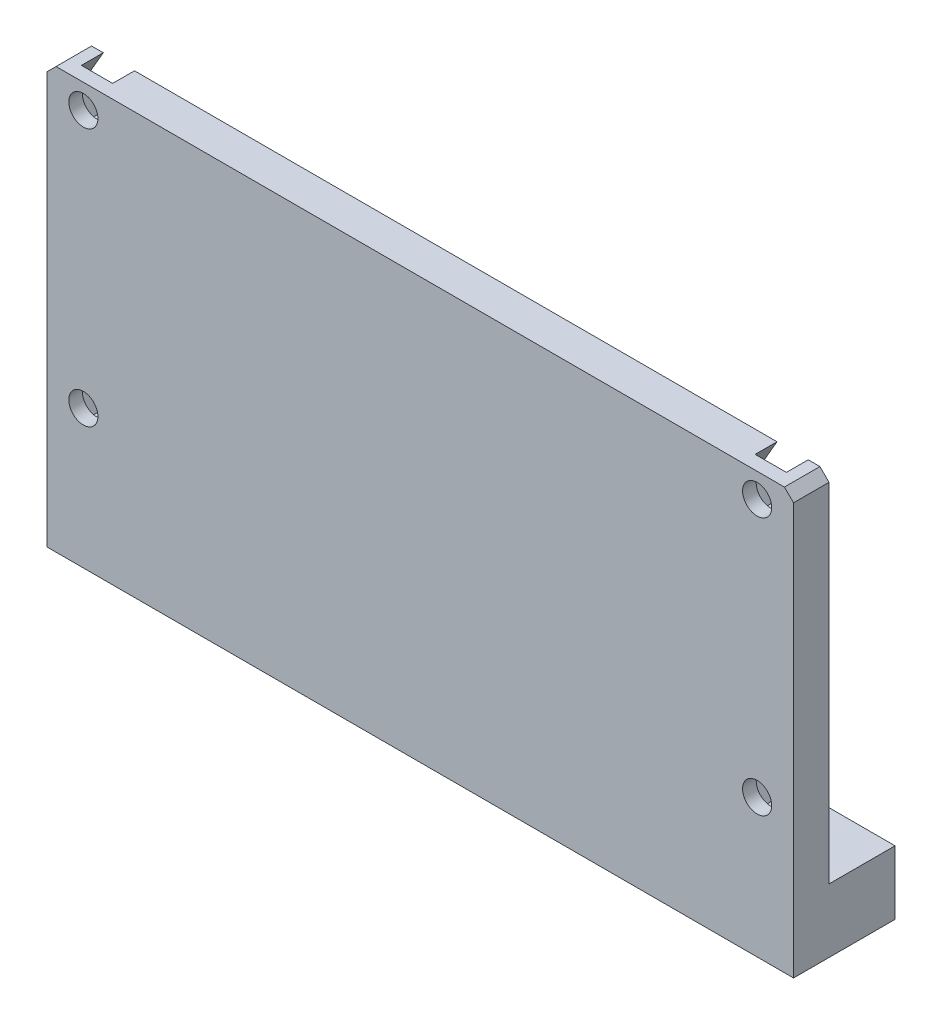
SolidWorks part; units mm, degrees
ref_plane "Front Plane" through (0, 0, 0) normal (0, 0, 1) x (1, 0, 0)
ref_plane "Top Plane" through (0, 0, 0) normal (0, 1, 0) x (1, 0, 0)
ref_plane "Right Plane" through (0, 0, 0) normal (1, 0, 0) x (0, 0, -1)
sketch "Sketch1" plane through (0, 0, 0) normal (0, 0, 1) x (1, 0, 0)
  line L0 (1, 11.6) -> (0, 10.6) construction
  line L1 (81, 11.6) -> (1, 11.6) construction
  line L2 (82, 10.6) -> (81, 11.6) construction
  line L3 (0, -35.2) -> (82, -35.2)
  line L4 (1, 11.6) -> (0, 10.6)
  line L5 (81, 11.6) -> (1, 11.6)
  line L6 (82, 10.6) -> (81, 11.6)
  line L9 (82, -35.2) -> (82, 10.6)
  line L10 (0, 10.6) -> (0, -35.2)
  line L11 (4, 8.9396) -> (4, -41.6656) construction
  circle A0 centre (4, 8.9396) radius 1.6 construction
  circle A1 centre (78, 8.9396) radius 1.6 construction
  circle A2 centre (4, -29.89) radius 1.6 construction
  circle A3 centre (4, 8.9396) radius 1.6
  circle A4 centre (78, 8.9396) radius 1.6
  dimension "D1" = 46.8
extrude "Boss-Extrude1" add sketch "Sketch1" along normal blind 11.15 contours A3 | L5 L4 L10 L3 L9 L6 | A4 region at (4, 8.9396, 0)
sketch "Sketch2" plane through (0, 0, 0) normal (0, 0, -1) x (-1, 0, 0)
  line L0 (0, -49.6) -> (-82, -49.6) construction
  line L1 (0, -49.6) -> (-82, -49.6) construction
  line L2 (-82, -54.6) -> (0, -54.6)
  line L3 (-82, -34.6) -> (0, -34.6)
  line L4 (-82, -35.2) -> (-82, 10.6) construction
  line L5 (0, 10.6) -> (0, -35.2) construction
  line L7 (0, -34.6) -> (0, -35.2)
  line L8 (-82, -35.2) -> (-82, -34.6)
  line L9 (-82, -35.2) -> (0, -35.2)
  dimension "D1" = 5
  dimension "D2" = 20
extrude "Cut-Extrude1" cut sketch "Sketch2" against normal blind 8 contours L3 L7 L9 L8
sketch "Sketch3" plane through (0, -34.6, 0) normal (0, -1, 0) x (1, 0, 0)
  line L0 (10.85, 4) -> (10.85, 0)
  line L1 (14.15, 4) -> (14.15, 0)
  line L2 (16.75, 4) -> (16.75, 0)
  line L3 (23.25, 4) -> (23.25, 0)
  line L4 (0, 0) -> (82, 0)
  line L5 (82, 0) -> (82, 8)
  line L6 (82, 8) -> (0, 8)
  line L7 (0, 8) -> (0, 0)
  line L8 (10.85, 0) -> (14.15, 0)
  line L9 (82, 0) -> (82, 8)
  line L10 (82, 8) -> (0, 8)
  line L11 (0, 8) -> (0, 0)
  line L12 (25.85, 4) -> (25.85, 0)
  line L13 (29.15, 4) -> (29.15, 0)
  line L14 (25.85, 0) -> (82, 0)
  line L15 (16.75, 0) -> (23.25, 0)
  arc A0 (14.15, 4) -> (10.85, 4) centre (12.5, 4) ccw
  arc A1 (23.25, 4) -> (16.75, 4) centre (20, 4) ccw
  arc A2 (29.15, 4) -> (25.85, 4) centre (27.5, 4) ccw
  line M5 (0, 0) -> (82, 0)
  dimension "D2" = 3.3
  dimension "D3" = 3.3
  dimension "D4" = 15
  dimension "D5" = 7.5
  dimension "D6" = 6.5
  dimension "D7" = 20
  dimension "D1" = 0
extrude "Cut-Extrude2" cut sketch "Sketch3" against normal up to next contours L13 A2 L12 M5 | A0 L0 L8 L1 | A1 L2 L15 L3 region at (27.5, -34.6, 2.6608)
sketch "Sketch4" plane through (0, 11.6, 0) normal (0, 1, 0) x (1, 0, 0)
  line L0 (9.25, -4) -> (9.25, 0)
  line L1 (10.85, 0) -> (1, 0) construction
  line L2 (15.75, -4) -> (15.75, 0)
  line L3 (16.75, 0) -> (14.15, 0) construction
  line L4 (15.75, 0) -> (9.25, 0)
  line L5 (24.25, -4) -> (24.25, 0)
  line L6 (25.85, 0) -> (23.25, 0) construction
  line L7 (24.25, 0) -> (30.75, 0)
  line L8 (81, 0) -> (29.15, 0) construction
  line L9 (30.75, 0) -> (30.75, -4)
  arc A0 (10.85, -4) -> (14.15, -4) centre (12.5, -4) ccw construction
  arc A1 (25.85, -4) -> (29.15, -4) centre (27.5, -4) ccw construction
  arc A2 (10.85, -4) -> (14.15, -4) centre (12.5, -4) ccw construction
  arc A3 (25.85, -4) -> (29.15, -4) centre (27.5, -4) ccw construction
  arc A4 (9.25, -4) -> (15.75, -4) centre (12.5, -4) ccw
  arc A5 (24.25, -4) -> (30.75, -4) centre (27.5, -4) ccw
  dimension "D1" = 6.5
  dimension "D2" = 6.5
extrude "Cut-Extrude3" cut sketch "Sketch4" against normal offset from surface (40.2 mm away) 6 up to face at (25.25, -34.6, 2.9094)
sketch "Sketch6" plane through (0, 11.6, 0) normal (0, 1, 0) x (1, 0, 0)
  line L0 (15.75, -4) -> (15.75, 0) construction
  line L1 (24.25, 0) -> (24.25, -4) construction
  line L2 (15.75, -4) -> (15.75, 0)
  line L3 (24.25, 0) -> (24.25, -4)
  line L4 (12.5, -7.25) -> (0, -7.25)
  line L5 (0, -11.15) -> (0, 0) construction
  line L6 (0, -7.25) -> (0, 1.0612)
  line L7 (0, 1.0612) -> (15.75, 1.0612)
  line L8 (15.75, 1.0612) -> (15.75, 0)
  line L9 (27.5, -7.25) -> (41, -7.25)
  line L10 (41, -7.25) -> (41, 0)
  line L11 (81, 0) -> (30.75, 0) construction
  line L12 (41, 0) -> (24.25, 0)
  arc A0 (9.25, -4) -> (15.75, -4) centre (12.5, -4) ccw construction
  arc A1 (24.25, -4) -> (30.75, -4) centre (27.5, -4) ccw construction
  arc A2 (12.5, -7.25) -> (15.75, -4) centre (12.5, -4) ccw
  arc A3 (24.25, -4) -> (27.5, -7.25) centre (27.5, -4) ccw
  dimension "D1" = 41
extrude "Cut-Extrude5" cut sketch "Sketch6" against normal offset from surface (39.2 mm away) 7 up to face at (25.25, -34.6, 2.9094)
ref_plane "Plane1" through (41, 0, 0) normal (-1, 0, 0) x (0, 0, 1)
mirror "Mirror1" about plane through (41, 0, 0) normal (-1, 0, 0) of "Cut-Extrude5", "Cut-Extrude3", "Cut-Extrude2", "Cut-Extrude1"
sketch "Sketch8" plane through (0, 0, 8) normal (0, 0, -1) x (-1, 0, 0)
  line L4 (-82, -34.6) -> (-82, -35.2)
  line L5 (-82, -35.2) -> (0, -35.2)
  line L6 (0, -35.2) -> (0, -34.6)
  line L7 (0, -34.6) -> (-82, -34.6)
  line L8 (-82, -34.6) -> (-82, -35.2)
  line L9 (-82, -35.2) -> (0, -35.2)
  line L10 (0, -35.2) -> (0, -34.6)
  line L11 (0, -34.6) -> (-82, -34.6)
  dimension "D1" = 0
sketch "Sketch9" plane through (0, 0, 0) normal (-1, 0, 0) x (0, 0, 1)
  line L2 (7.25, 11.6) -> (0, 2.4)
  line L3 (0, 11.6) -> (7.25, 11.6)
sketch "Sketch12" plane through (0, 11.6, 0) normal (0, 1, 0) x (1, 0, 0)
  line L0 (16.75, -4) -> (16.75, 0)
  line L1 (16.75, 0) -> (18, 0)
  line L2 (23.25, 0) -> (23.25, -4)
  line L5 (22, 0) -> (23.25, 0)
  line L6 (58.75, -4) -> (58.75, 0)
  line L7 (58.75, 0) -> (60.05, 0)
  line L8 (65.25, 0) -> (65.25, -4) construction
  line L9 (65.25, 0) -> (65.25, -4)
  line L10 (60.05, 0) -> (60.155, -3.1064)
  line L11 (18, 0) -> (18.11, -3.0846)
  line L12 (63.95, 0) -> (65.25, 0)
  line L13 (22, 0) -> (21.89, -3.0846)
  line L15 (63.95, 0) -> (63.845, -3.1064)
  arc A0 (16.75, -4) -> (23.25, -4) centre (20, -4) ccw construction
  arc A1 (58.75, -4) -> (65.25, -4) centre (62, -4) ccw construction
  arc A2 (16.75, -4) -> (23.25, -4) centre (20, -4) ccw
  arc A3 (58.75, -4) -> (65.25, -4) centre (62, -4) ccw
  arc A4 (18.11, -3.0846) -> (21.89, -3.0846) centre (20, -4) ccw
  arc A5 (60.155, -3.1064) -> (63.845, -3.1064) centre (62, -4) ccw
  dimension "D1" = 1.25
  dimension "D2" = 4.1
  dimension "D3" = 1.3
  dimension "D4" = 1.3
  dimension "D5" = 1.25
extrude "Boss-Extrude2" add sketch "Sketch12" against normal offset from surface (32.2 mm away) 7 up to face at (41, -27.6, 3.9744)
chamfer "Chamfer3" distance 1.1 angle 45 3 edges at (58.75, -20.6, 2) (65.25, -20.6, 2) (62, -20.6, 7.25)
chamfer "Chamfer4" distance 1.1 angle 45 3 edges at (16.75, -20.6, 2) (23.25, -20.6, 2) (20, -20.6, 7.25)
extrude "Cut-Extrude12" cut sketch "Sketch9" against normal through all and the other way through all flip side to cut contours L3 L2
fillet "Fillet3" radius 15 4 edges at (16.875, 2.4, 0) (23.125, 2.4, 0) (58.9, 2.4, 0) (65.1, 2.4, 0)
sketch "Sketch13" plane through (0, 0, 7.25) normal (0, 0, -1) x (-1, 0, 0)
  circle A0 centre (-78, 8.9396) radius 2.85
  dimension "D1" = 5.7
sketch "Sketch14" plane through (0, 0, 11.15) normal (0, 0, 1) x (1, 0, 0)
  circle A0 centre (4, -19.4004) radius 1.6 construction
  circle A1 centre (4, -19.4004) radius 1.6
extrude "Cut-Extrude14" cut sketch "Sketch14" against normal through all contours A1
mirror "Mirror3" about plane through (41, 0, 0) normal (-1, 0, 0) of "Cut-Extrude14"
sketch "Sketch18" plane through (0, -27.6, 0) normal (0, 1, 0) x (1, 0, 0)
  line L6 (14.15, 0) -> (14.15, -4)
  line L7 (10.85, -4) -> (10.85, 0)
  line L8 (10.85, 0) -> (9.25, 0)
  line L9 (9.25, 0) -> (9.25, -4)
  line L10 (15.75, -4) -> (15.75, 0)
  line L11 (15.75, 0) -> (14.15, 0)
  line L12 (14.15, 0) -> (14.15, -1.2)
  line L13 (10.85, -1.2) -> (10.85, 0)
  line L14 (10.85, 0) -> (9.25, 0)
  line L15 (9.25, 0) -> (9.25, -4)
  line L16 (15.75, -4) -> (15.75, 0)
  line L17 (15.75, 0) -> (14.15, 0)
  line L18 (29.15, 0) -> (29.15, -4)
  line L19 (25.85, -4) -> (25.85, 0)
  line L20 (25.85, 0) -> (24.25, 0)
  line L21 (24.25, 0) -> (24.25, -4)
  line L22 (30.75, -4) -> (30.75, 0)
  line L23 (30.75, 0) -> (29.15, 0)
  line L24 (29.15, 0) -> (29.15, -1.2)
  line L25 (25.85, -1.2) -> (25.85, 0)
  line L26 (25.85, 0) -> (24.25, 0)
  line L27 (24.25, 0) -> (24.25, -4)
  line L28 (30.75, -4) -> (30.75, 0)
  line L29 (30.75, 0) -> (29.15, 0)
  arc A0 (10.85, -1.2) -> (9.25, -4) centre (12.5, -4) ccw
  arc A1 (15.75, -4) -> (14.15, -1.2) centre (12.5, -4) ccw
  arc A2 (10.85, -4) -> (14.15, -4) centre (12.5, -4) ccw
  arc A3 (9.25, -4) -> (15.75, -4) centre (12.5, -4) ccw
  arc A4 (25.85, -1.2) -> (24.25, -4) centre (27.5, -4) ccw
  arc A5 (30.75, -4) -> (29.15, -1.2) centre (27.5, -4) ccw
  arc A6 (25.85, -4) -> (29.15, -4) centre (27.5, -4) ccw
  arc A7 (24.25, -4) -> (30.75, -4) centre (27.5, -4) ccw
  dimension "D1" = 0
  dimension "D2" = 0
extrude "Boss-Extrude3" add sketch "Sketch18" against normal blind 3.5
mirror "Mirror5" about plane through (41, 0, 0) normal (-1, 0, 0) of "Boss-Extrude3"
sketch "Sketch19" plane through (0, 0, 7.25) normal (0, 0, -1) x (-1, 0, 0)
  circle A0 centre (-78, -19.4004) radius 2.85
extrude "Cut-Extrude16" cut sketch "Sketch8" against normal through all contours L11 L8 L9 L10
sketch "Sketch20" plane through (0, 0, 7.25) normal (0, 0, -1) x (-1, 0, 0)
  line L1 (-76.375, 11.7542) -> (-79.625, 11.7542)
  line L2 (-79.625, 11.7542) -> (-81.25, 8.9396)
  line L3 (-81.25, 8.9396) -> (-79.625, 6.1251)
  line L4 (-79.625, 6.1251) -> (-76.375, 6.1251)
  line L5 (-76.375, 6.1251) -> (-74.75, 8.9396)
  line L6 (-74.75, 8.9396) -> (-76.375, 11.7542)
  line L7 (-79.625, -16.5858) -> (-81.25, -19.4004)
  line L8 (-81.25, -19.4004) -> (-79.625, -22.2149)
  line L9 (-79.625, -22.2149) -> (-76.375, -22.2149)
  line L10 (-76.375, -22.2149) -> (-74.75, -19.4004)
  line L11 (-74.75, -19.4004) -> (-76.375, -16.5858)
  line L12 (-76.375, -16.5858) -> (-79.625, -16.5858)
  circle A0 centre (-78, 8.9396) radius 3.25 construction
  circle A2 centre (-78, -19.4004) radius 3.25 construction
  dimension "D1" = 6.5
  dimension "D2" = 6.5
extrude "Cut-Extrude17" cut sketch "Sketch20" against normal blind 2.4
mirror "Mirror7" about plane through (41, 0, 0) normal (-1, 0, 0) of "Cut-Extrude17"
